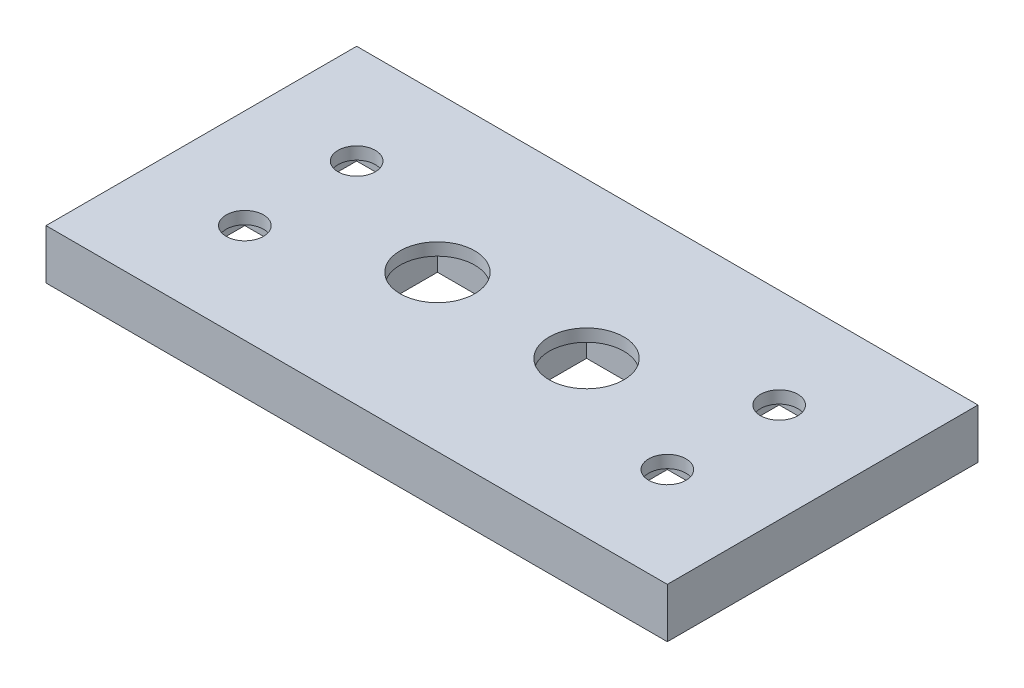
SolidWorks part; units mm, degrees
ref_plane "Front Plane" through (0, 0, 0) normal (0, 0, 1) x (1, 0, 0)
ref_plane "Top Plane" through (0, 0, 0) normal (0, 1, 0) x (1, 0, 0)
ref_plane "Right Plane" through (0, 0, 0) normal (1, 0, 0) x (0, 0, -1)
sketch "Sketch1" plane through (0, 0, 0) normal (0, 1, 0) x (1, 0, 0)
  line L0 (0, 12.5) -> (50, 12.5) construction
  line L1 (0, 0) -> (50, 0)
  line L2 (0, 0) -> (0, 25)
  line L3 (0, 25) -> (50, 25)
  line L4 (50, 0) -> (50, 25)
  line L5 (25, 25) -> (25, 0) construction
  line L6 (4, 4) -> (12, 4)
  line L7 (15, 8.5) -> (23, 8.5)
  line L8 (15, 8.5) -> (15, 16.5)
  line L9 (15, 16.5) -> (23, 16.5)
  line L10 (23, 8.5) -> (23, 16.5)
  line L11 (15, 8.5) -> (23, 16.5) construction
  line L12 (15, 16.5) -> (23, 8.5) construction
  line L13 (4, 13) -> (12, 13)
  line L14 (4, 13) -> (4, 21)
  line L15 (4, 21) -> (12, 21)
  line L16 (12, 13) -> (12, 21)
  line L17 (4, 13) -> (12, 21) construction
  line L18 (4, 21) -> (12, 13) construction
  line L19 (12, 12) -> (12, 4)
  line L20 (4, 12) -> (12, 12)
  line L21 (4, 12) -> (4, 4)
  line L22 (35, 16.5) -> (27, 16.5)
  line L23 (27, 8.5) -> (27, 16.5)
  line L24 (35, 8.5) -> (27, 8.5)
  line L25 (35, 8.5) -> (35, 16.5)
  line L26 (46, 12) -> (46, 4)
  line L27 (46, 12) -> (38, 12)
  line L28 (38, 12) -> (38, 4)
  line L29 (46, 4) -> (38, 4)
  line L30 (46, 13) -> (46, 21)
  line L31 (46, 21) -> (38, 21)
  line L32 (46, 13) -> (38, 13)
  line L33 (38, 13) -> (38, 21)
  circle A0 centre (8, 17) radius 1.5
  circle A1 centre (19, 12.5) radius 3
  circle A2 centre (8, 8) radius 1.5
  circle A3 centre (31, 12.5) radius 3
  circle A4 centre (42, 8) radius 1.5
  circle A5 centre (42, 17) radius 1.5
  point P9 (19, 12.5)
  point P14 (8, 17)
  dimension "D4" = 3
  dimension "D8" = 6
  dimension "D1" = 50
  dimension "D2" = 25
  dimension "D3" = 8
  dimension "D5" = 6
  dimension "D6" = 4.5
  dimension "D7" = 17
extrude "Boss-Extrude1" add sketch "Sketch1" along normal blind 4 contours L1 L4 L3 L2
extrude "Cut-Extrude3" cut sketch "Sketch1<3>" along normal blind 3 contours L29 L26 L27 L28 A4 | L33 L32 L30 L31 A5 | L24 L25 L22 L23 A3 | L20 L21 L6 L19 A2 | L8 L9 L10 L7 | L14 L15 L16 L13 region at (4.1131, 0, -8) region at (34.8869, 0, -12.5) region at (45.8869, 0, -8) region at (42, 0, -13.1131)
sketch "Sketch1<3>" plane through (0, 0, 0) normal (0, 1, 0) x (1, 0, 0) same geometry as "Sketch1"
extrude "Cut-Extrude4" cut sketch "Sketch1<4>" along normal through all contours A0 | A5 | A4 | A3 | A1 | A2 region at (8, 0, -17)
sketch "Sketch1<4>" plane through (0, 0, 0) normal (0, 1, 0) x (1, 0, 0) same geometry as "Sketch1"
